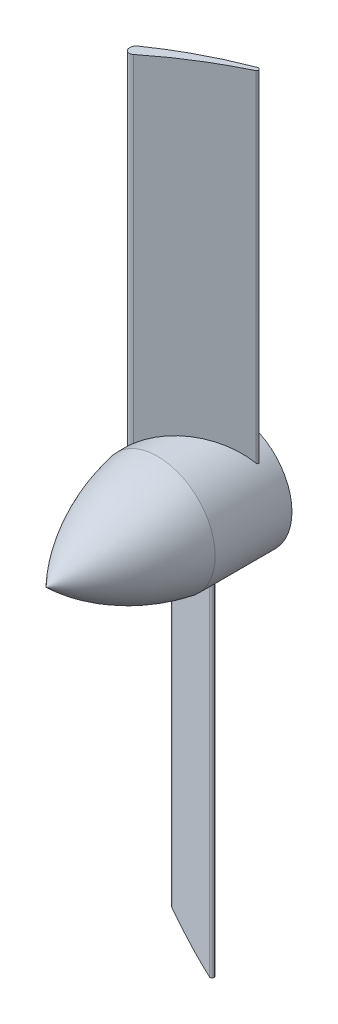
SolidWorks part; units mm, degrees
ref_plane "Front Plane" through (0, 0, 0) normal (0, 0, 1) x (1, 0, 0)
ref_plane "Top Plane" through (0, 0, 0) normal (0, 1, 0) x (1, 0, 0)
ref_plane "Right Plane" through (0, 0, 0) normal (1, 0, 0) x (0, 0, -1)
sketch "Sketch1" plane through (0, 0, 0) normal (0, 1, 0) x (1, 0, 0)
  line L0 (-1000, 0) -> (49000, 0) construction
  line L1 (0, -1000) -> (0, 49000) construction
  line L2 (-11.677, -21.6393) -> (13.041, -5.9033)
  line L3 (-13.5802, -18.3429) -> (12.4066, -4.8045)
  arc A0 (13.041, -5.9033) -> (12.4066, -4.8045) centre (12.7, -5.3677) ccw
  arc A1 (-13.5802, -18.3429) -> (-11.677, -21.6393) centre (-12.7, -20.0323) ccw
  dimension "D1" = 1.27
  dimension "D2" = 3.81
  dimension "D3" = 5.3677
  dimension "D4" = 25.4
  dimension "D5" = 12.7
  dimension "D6" = 14.6647
extrude "Boss-Extrude1" add sketch "Sketch1" along normal blind 127
sketch "Sketch3" plane through (0, 0, 0) normal (0, 1, 0) x (1, 0, 0)
  line L0 (-20.3071, -20.0323) -> (28.6538, -20.0323) construction
  line L1 (-13.5802, -7.0571) -> (12.4066, -20.5955)
  line L2 (-1000, 0) -> (49000, 0) construction
  line L3 (0, -1000) -> (0, 49000) construction
  line L4 (-11.677, -3.7607) -> (13.041, -19.4967)
  arc A0 (-11.677, -3.7607) -> (-13.5802, -7.0571) centre (-12.7, -5.3677) ccw
  arc A1 (12.4066, -20.5955) -> (13.041, -19.4967) centre (12.7, -20.0323) ccw
  dimension "D1" = 3.81
  dimension "D2" = 1.27
  dimension "D3" = 5.3677
  dimension "D4" = 14.6647
  dimension "D5" = 25.4
  dimension "D6" = 12.7
extrude "Boss-Extrude2" add sketch "Sketch3" against normal blind 127
sketch "Sketch4" plane through (0, 0, 0) normal (0, 0, 1) x (1, 0, 0)
  circle A0 centre (0, 0) radius 127
  circle A1 centre (0, 0) radius 136.4346
  dimension "D1" = 254
extrude "Cut-Extrude1" cut sketch "Sketch4" against normal blind 127 and the other way blind 127
sketch "Sketch5" plane through (0, 0, 0) normal (1, 0, 0) x (0, 0, -1)
  line L0 (0, -1000) -> (0, 49000) construction
  line L1 (-1000, 0) -> (49000, 0) construction
  line L2 (-12.7, 0) -> (-12.7, 12.7)
  line L3 (0, 12.7) -> (0, 19.05)
  line L4 (-12.7, 12.7) -> (0, 12.7)
  line L5 (0, 19.05) -> (-25.4, 19.05)
  line L6 (-12.7, 0) -> (-62.3062, 0)
  arc A0 (0, -120.9037) -> (36.9986, 0) centre (-12.6538, -50.9185) ccw
  arc A1 (-25.4, 19.05) -> (-62.3062, 0) centre (-12.6538, -50.9185) ccw
  dimension "D5" = 71.12
  dimension "D1" = 12.7
  dimension "D2" = 12.7
  dimension "D3" = 19.05
  dimension "D4" = 25.4
  dimension "D6" = 62.3062
revolve "Revolve1" add sketch "Sketch5" angle 360 about L1
sketch "Sketch6" plane through (0, 0, 0) normal (0, 0, -1) x (-1, 0, 0)
  circle A0 centre (0, 0) radius 12.7
extrude "Cut-Extrude2" cut sketch "Sketch6" against normal blind 12.7
